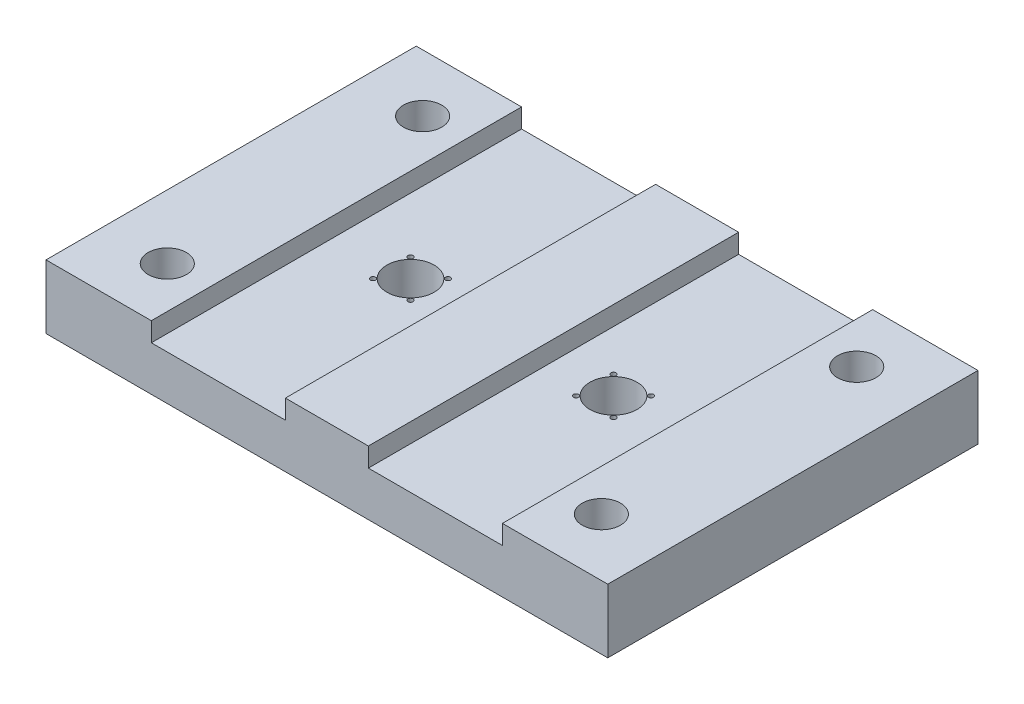
SolidWorks part; units mm, degrees
ref_plane "Front Plane" through (0, 0, 0) normal (0, 0, 1) x (1, 0, 0)
ref_plane "Top Plane" through (0, 0, 0) normal (0, 1, 0) x (1, 0, 0)
ref_plane "Right Plane" through (0, 0, 0) normal (1, 0, 0) x (0, 0, -1)
sketch "Sketch1" plane through (0, 0, 0) normal (0, 1, 0) x (1, 0, 0)
  line L1 (-440, 290) -> (440, 290)
  line L2 (-440, 290) -> (-440, -290)
  line L3 (-440, -290) -> (440, -290)
  line L4 (440, 290) -> (440, -290)
  line L6 (-440, 0) -> (440, 0) construction
  point P0 (0, 0)
  dimension "D1" = 440
  dimension "D2" = 440
extrude "Boss-Extrude1" add sketch "Sketch1" along normal blind 100
sketch "Sketch2" plane through (0, 100, 0) normal (0, 1, 0) x (1, 0, 0)
  line L0 (-440, -290) -> (440, -290) construction
  line L1 (-225, 290) -> (-65, 290)
  line L2 (-225, 290) -> (-225, -290)
  line L3 (-225, -290) -> (-65, -290)
  line L4 (225, 290) -> (225, -290)
  line L6 (-225, 0) -> (-65, 0) construction
  line L7 (-65, 290) -> (-65, -290)
  line L8 (65, 290) -> (65, -290)
  line L9 (65, -290) -> (225, -290)
  line L10 (65, 0) -> (225, 0) construction
  line L11 (65, 290) -> (225, 290)
  point P0 (0, 0)
  dimension "D1" = 160
extrude "Cut-Extrude1" cut sketch "Sketch2" against normal blind 30
sketch "Sketch3" plane through (0, 100, 0) normal (0, 1, 0) x (1, 0, 0)
  line L0 (225, -290) -> (440, -290) construction
  line L1 (65, 290) -> (275, 290)
  line L2 (65, 290) -> (65, -290)
  line L3 (65, -290) -> (275, -290)
  line L4 (275, 290) -> (275, -290)
  line L5 (-225, 290) -> (-440, 290) construction
  line L6 (-65, -290) -> (-275, -290)
  line L7 (-65, -290) -> (-65, 290)
  line L8 (-65, 290) -> (-275, 290)
  line L9 (-275, -290) -> (-275, 290)
extrude "Cut-Extrude2" cut sketch "Sketch3" against normal blind 30
sketch "Sketch4" plane through (0, 70, 0) normal (0, 1, 0) x (1, 0, 0)
  circle A0 centre (-159, 0) radius 37
  circle A1 centre (159, 0) radius 37
  dimension "D1" = 159
  dimension "D2" = 159
extrude "Cut-Extrude3" cut sketch "Sketch4" against normal blind 264
sketch "Sketch6" plane through (0, 100, 0) normal (0, 1, 0) x (1, 0, 0)
  circle A0 centre (-340, 200) radius 30
  circle A1 centre (340, 200) radius 30
  circle A2 centre (340, -200) radius 30
  circle A3 centre (-340, -200) radius 30
  dimension "D1" = 680
  dimension "D2" = 340
  dimension "D3" = 200
extrude "Cut-Extrude5" cut sketch "Sketch6" against normal blind 271
sketch "Sketch7" plane through (0, 0, 0) normal (0, -1, 0) x (1, 0, 0)
  circle A0 centre (-340, 200) radius 35
  circle A1 centre (340, 200) radius 35
  circle A2 centre (-340, -200) radius 35
  circle A3 centre (340, -200) radius 35
extrude "Cut-Extrude6" cut sketch "Sketch7" against normal blind 10
sketch "Sketch9" plane through (0, 0, 0) normal (0, -1, 0) x (1, 0, 0)
  circle A0 centre (-129.6551, 29.3449) radius 4
  point P0 (-159, 0)
extrude "Cut-Extrude14" cut sketch "Sketch9" against normal blind 500
ref_axis "Axis1" through (-159, 0, 0) along (0, 1, 0)
pattern_circular "CirPattern2" count 4 over 360 about axis through (-159, 0, 0) along (0, 1, 0) of "Cut-Extrude14"
mirror "Mirror2" about plane through (0, 0, 0) normal (1, 0, 0) of "CirPattern2"
